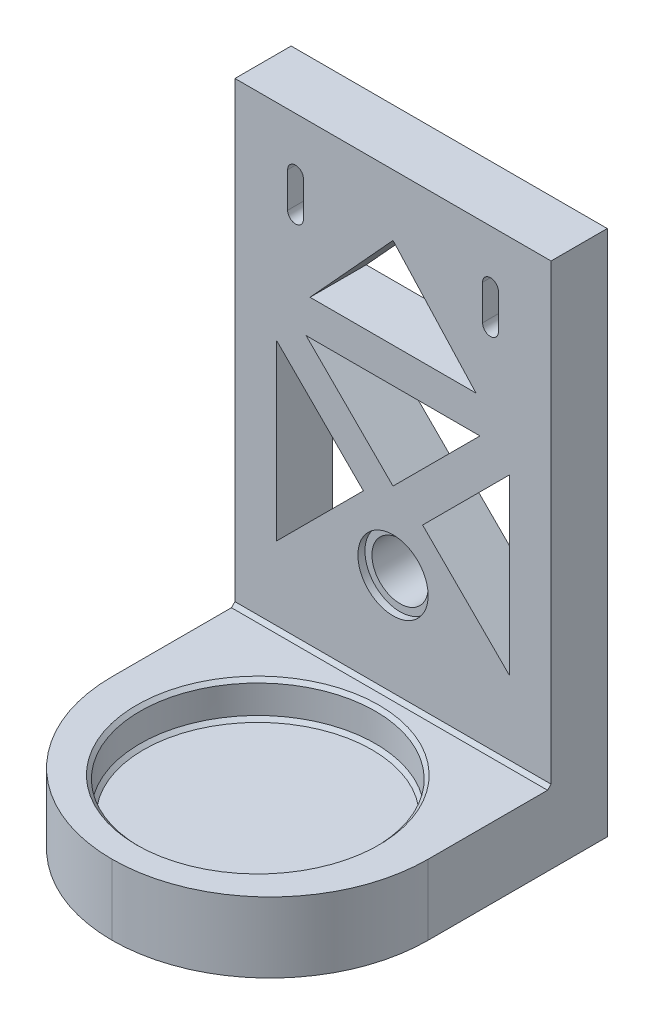
SolidWorks part; units mm, degrees
ref_plane "Front Plane" through (0, 0, 0) normal (0, 0, 1) x (1, 0, 0)
ref_plane "Top Plane" through (0, 0, 0) normal (0, 1, 0) x (1, 0, 0)
ref_plane "Right Plane" through (0, 0, 0) normal (1, 0, 0) x (0, 0, -1)
sketch "Sketch1" plane through (0, 0, 0) normal (0, 0, 1) x (1, 0, 0)
  line L0 (0, 150) -> (0, 0) construction
  line L1 (45, 0) -> (-45, 0)
  line L2 (45, 0) -> (45, 150)
  line L3 (45, 150) -> (-45, 150)
  line L4 (-45, 0) -> (-45, 150)
  line L5 (-27.75, 135) -> (-27.75, 125) construction
  line L6 (-25.5, 135) -> (-25.5, 125)
  line L7 (-30, 135) -> (-30, 125)
  line L8 (27.75, 135) -> (27.75, 125) construction
  line L9 (25.5, 135) -> (25.5, 125)
  line L10 (30, 135) -> (30, 125)
  arc A3 (-25.5, 135) -> (-30, 135) centre (-27.75, 135) ccw
  arc A4 (-30, 125) -> (-25.5, 125) centre (-27.75, 125) ccw
  arc A5 (25.5, 135) -> (30, 135) centre (27.75, 135) cw
  arc A6 (30, 125) -> (25.5, 125) centre (27.75, 125) cw
  point P11 (-27.75, 130)
  point P16 (27.75, 130)
  dimension "D3" = 4.5
  dimension "D4" = 10
  dimension "D6" = 15
  dimension "D1" = 150
  dimension "D2" = 90
  dimension "D7" = 15
extrude "Boss-Extrude1" add sketch "Sketch1" along normal blind 16
sketch "Sketch4" plane through (0, 0, 0) normal (0, 1, 0) x (1, 0, 0)
  line L0 (45, -16) -> (-45, -16) construction
  line L1 (-45, -16) -> (45, -16)
  line L2 (-45, -16) -> (-45, -96)
  line L3 (-45, -96) -> (45, -96)
  line L4 (45, -16) -> (45, -96)
  line L6 (0, -16) -> (0, -96) construction
  line L7 (-45, -56) -> (45, -56) construction
  dimension "D1" = 80
  dimension "D2" = 90
sketch "Sketch5" plane through (0, 0, 16) normal (0, 0, 1) x (1, 0, 0)
  line L0 (0, 0) -> (0, 150) construction
  line L1 (45, 150) -> (-45, 150) construction
  line L2 (-45, 75) -> (45, 75) construction
  line L3 (-45, 150) -> (-45, 0) construction
  line L4 (45, 0) -> (45, 150) construction
  circle A0 centre (0, 50) radius 10
  dimension "D1" = 20
  dimension "D2" = 50
extrude "Boss-Extrude2" add sketch "Sketch4" along normal blind 20 contours L2 L3 L4 L1
sketch "Sketch6" plane through (0, 20, 0) normal (0, 1, 0) x (1, 0, 0)
  line L0 (-10, -16) -> (10, -16) construction
  circle A0 centre (0, -54.5) radius 33.5
  point P0 (0, -21)
  point P1 (0, -16)
  dimension "D1" = 67
  dimension "D2" = 5
extrude "Cut-Extrude1" cut sketch "Sketch6" against normal blind 10 contours A0
fillet "Fillet1" radius 45 2 edges at (45, 10, 96) (-45, 10, 96)
sketch "Sketch7" plane through (0, 0, 16) normal (0, 0, 1) x (1, 0, 0)
  circle A0 centre (0, 50) radius 8
  dimension "D1" = 16
extrude "Cut-Extrude4" cut sketch "Sketch7" against normal through all
extrude "Cut-Extrude5" cut sketch "Sketch5" against normal blind 2
chamfer "Chamfer3" distance 1 angle 45 1 edges at (0, 20, 16)
chamfer "Chamfer4" distance 1 angle 45 2 edges at (0, 10, 88) (0, 20, 88)
sketch "Sketch8" plane through (0, 0, 16) normal (0, 0, 1) x (1, 0, 0)
  line L0 (-33.1763, 91.3545) -> (-8.4275, 66.6057)
  line L1 (-8.4275, 66.6057) -> (-33.1763, 41.857)
  line L2 (-33.1763, 41.857) -> (-33.1763, 91.3545)
  line L3 (0, 150) -> (0, 21) construction
  line L4 (45, 150) -> (-45, 150) construction
  line L12 (8.4275, 66.6057) -> (33.1763, 41.857)
  line L13 (33.1763, 91.3545) -> (8.4275, 66.6057)
  line L14 (33.1763, 41.857) -> (33.1763, 91.3545)
  line L18 (24.7487, 96.7375) -> (0, 71.9887)
  line L19 (0, 71.9887) -> (-24.7487, 96.7375)
  line L20 (-24.7487, 96.7375) -> (24.7487, 96.7375)
  line L21 (-45, 21) -> (45, 21) construction
  line L22 (23.6237, 106.7375) -> (-23.6237, 106.7375)
  line L23 (-23.6237, 106.7375) -> (0, 132.5623)
  line L24 (0, 132.5623) -> (23.6237, 106.7375)
  point P7 (0, 0)
  dimension "D1" = 35
  dimension "D2" = 35
  dimension "D3" = 35
  dimension "D4" = 35
  dimension "D5" = 35
  dimension "D6" = 35
  dimension "D7" = 10
  dimension "D8" = 10
  dimension "D9" = 10
extrude "Cut-Extrude8" cut sketch "Sketch8" against normal through all
